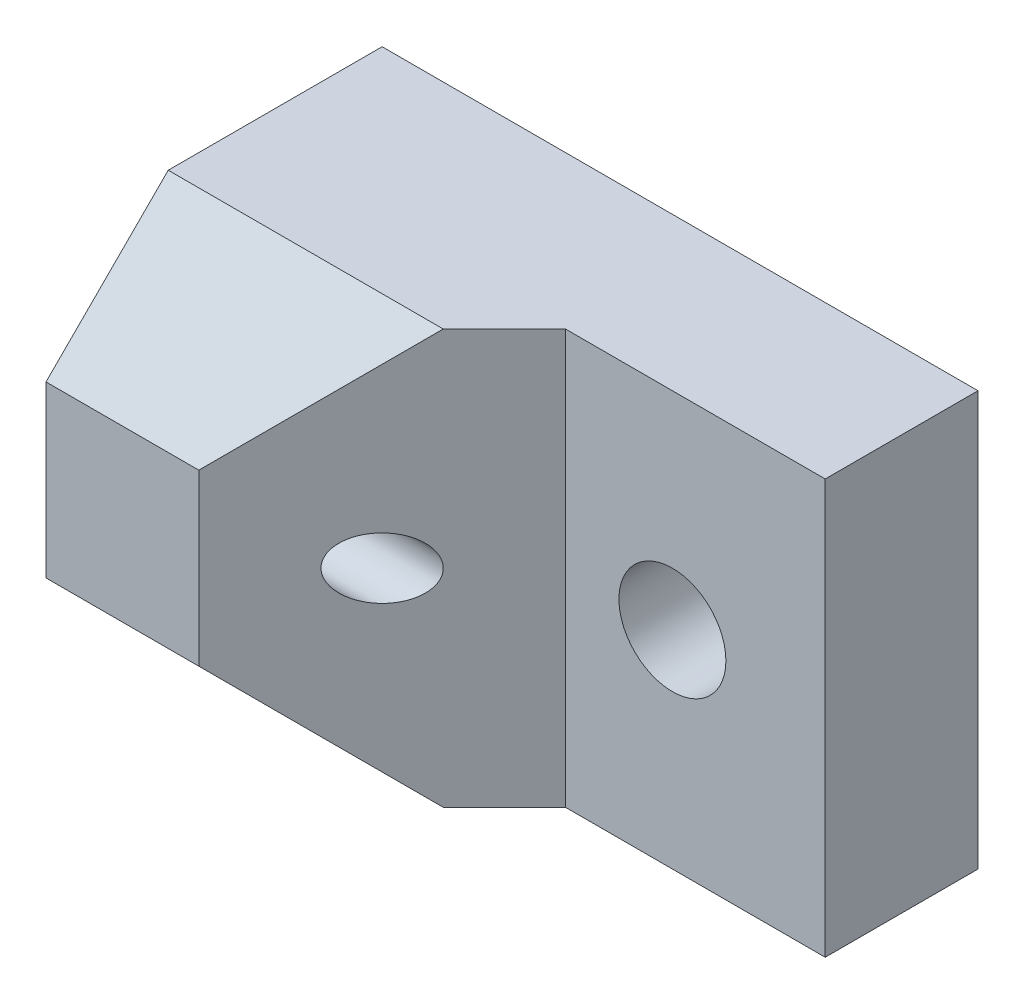
SolidWorks part; units mm, degrees
ref_plane "Top Plane" through (0, 0, 0) normal (0, 0, 1) x (1, 0, 0)
ref_plane "Right Plane" through (0, 0, 0) normal (0, 1, 0) x (1, 0, 0)
ref_plane "Front Plane" through (0, 0, 0) normal (1, 0, 0) x (0, 0, -1)
sketch "Sketch1" plane through (0, 0, 0) normal (0, 0, 1) x (1, 0, 0)
  line L0 (-21.1642, -9) -> (-40.35, -9) construction
  line L1 (-35.4219, -9) -> (-15.9219, -9)
  line L2 (-35.4219, -9) -> (-35.4219, -22.5563)
  line L3 (-35.4219, -22.5563) -> (-15.9219, -22.5563)
  line L4 (-15.9219, -9) -> (-15.9219, -22.5563)
  line L5 (-42.85, -22.5563) -> (-12.85, -22.5563) construction
  circle A0 centre (-20.9219, -15.7782) radius 1.75
  dimension "D1" = 3.5
  dimension "D2" = 5
  dimension "D3" = 19.5
extrude "Boss-Extrude1" add sketch "Sketch1" along normal blind 5
sketch "Sketch2" plane through (0, 0, 0) normal (0, 0, -1) x (-1, 0, 0)
  line L0 (28.9219, -15.7782) -> (20.9219, -15.7782) construction
  line L1 (28.9219, -17.7782) -> (35.9219, -17.7782) construction
  line L2 (28.9219, -17.7782) -> (28.9219, -13.7782) construction
  line L3 (28.9219, -13.7782) -> (35.9219, -13.7782) construction
  line L4 (35.9219, -17.7782) -> (35.9219, -13.7782) construction
  line L5 (29.4219, -17.2782) -> (29.4219, -14.2782)
  line L6 (29.4219, -14.2782) -> (35.4219, -14.2782)
  line L7 (35.4219, -17.2782) -> (35.4219, -14.2782)
  line L8 (29.4219, -17.2782) -> (35.4219, -17.2782)
  circle A0 centre (20.9219, -15.7782) radius 1.75 construction
  dimension "D1" = 7
  dimension "D2" = 8
  dimension "D3" = 4
  dimension "D4" = 0.5
extrude "Boss-Extrude2" add sketch "Sketch2" along normal blind 2
sketch "Sketch3" plane through (-35.4219, 0, 0) normal (-1, 0, 0) x (0, 0, 1)
  line L0 (8, -9) -> (8, -22.5563) construction
  line L1 (5, -9) -> (11, -9)
  line L2 (5, -9) -> (5, -22.5563)
  line L3 (5, -22.5563) -> (11, -22.5563)
  line L4 (11, -9) -> (11, -22.5563)
  circle A0 centre (8, -15.7782) radius 1
  dimension "D1" = 2
  dimension "D2" = 6
extrude "Boss-Extrude3" add sketch "Sketch3" against normal blind 5
chamfer "Chamfer1" distance 4 angle 45 2 edges at (-32.9219, -22.5563, 11) (-32.9219, -9, 11)
chamfer "Chamfer2" distance 6 angle 45 1 edges at (-30.4219, -15.7782, 5)
